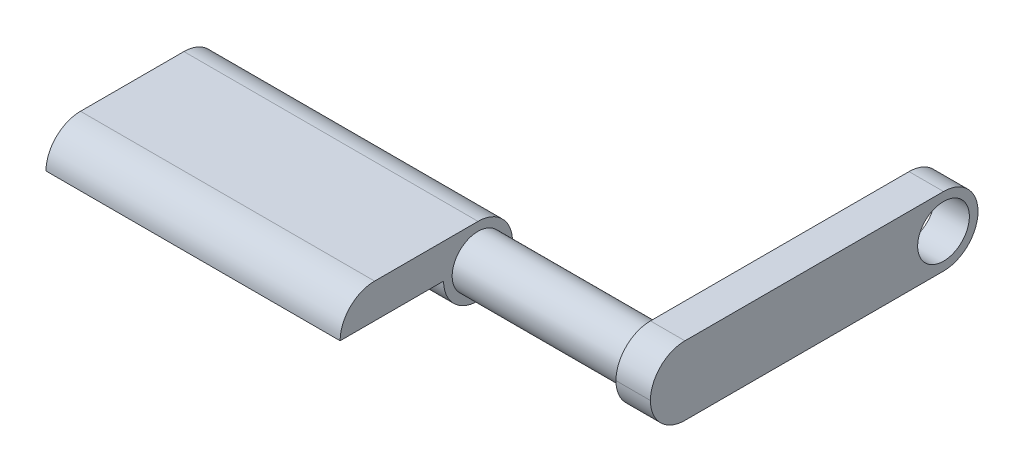
SolidWorks part; units mm, degrees
material "Nickel"
ref_plane "Front Plane" through (0, 0, 0) normal (0, 0, 1) x (1, 0, 0)
ref_plane "Top Plane" through (0, 0, 0) normal (0, 1, 0) x (1, 0, 0)
ref_plane "Right Plane" through (0, 0, 0) normal (1, 0, 0) x (0, 0, -1)
sketch "Sketch2" plane through (0, 0, 0) normal (1, 0, 0) x (0, 0, -1)
  circle A0 centre (0, 0) radius 2
  dimension "D1" = 4
extrude "Boss-Extrude1" add sketch "Sketch2" along normal blind 17.06
sketch "Sketch3" plane through (17.06, 0, 0) normal (1, 0, 0) x (0, 0, -1)
  circle A0 centre (0, 0) radius 1.5
  dimension "D1" = 3
extrude "Boss-Extrude2" add sketch "Sketch3" along normal blind 12
sketch "Sketch4" plane through (29.06, 0, 0) normal (1, 0, 0) x (0, 0, -1)
  line L1 (-2, 2) -> (1.9881, 2)
  line L2 (-2, 2) -> (-2, -2)
  line L3 (-2, -2) -> (1.9881, -2)
  line L4 (1.9881, 2) -> (1.9881, -2)
  circle A0 centre (0, 0) radius 2 construction
extrude "Boss-Extrude3" add sketch "Sketch4" against normal blind 2
sketch "Sketch5" plane through (0, 0, 2) normal (0, 0, 1) x (1, 0, 0)
  line L1 (29.06, 2) -> (27.06, 2)
  line L2 (29.06, 2) -> (29.06, -2)
  line L3 (29.06, -2) -> (27.06, -2)
  line L4 (27.06, 2) -> (27.06, -2)
extrude "Boss-Extrude4" add sketch "Sketch5" against normal blind 19
fillet "Fillet1" radius 2 1 edges at (28.06, 2, 2)
fillet "Fillet2" radius 2 1 edges at (28.06, -2, 2)
fillet "Fillet3" radius 2 2 edges at (28.06, -2, -17) (28.06, 2, -17)
sketch "Sketch6" plane through (29.06, 0, 0) normal (1, 0, 0) x (0, 0, -1)
  circle A0 centre (15, 0) radius 1.5
  arc A1 (17, 0) -> (15, 2) centre (15, 0) ccw construction
  dimension "D1" = 3
extrude "Cut-Extrude1" cut sketch "Sketch6" against normal through all
sketch "Sketch7" plane through (29.06, 0, 0) normal (1, 0, 0) x (0, 0, -1)
  line L0 (17, 0) -> (22, -8.6603)
  line L1 (13.5359, -2) -> (18.5359, -10.6603)
  line L2 (0, -2) -> (15, -2) construction
  line L3 (13.5359, -2) -> (15, -2)
  line L4 (18.5359, -10.6603) -> (22, -8.6603)
  line L6 (0, -2) -> (15, -2)
  line L7 (15, 2) -> (0, 2)
  line L8 (0, -2) -> (13.5359, -2)
  line L9 (15, 2) -> (0, 2)
  circle A0 centre (15, 0) radius 2
  arc A4 (15, -2) -> (17, 0) centre (15, 0) ccw
  arc A5 (17, 0) -> (15, 2) centre (15, 0) ccw
  arc A6 (0, 2) -> (-2, 0) centre (0, 0) ccw
  arc A7 (-2, 0) -> (0, -2) centre (0, 0) ccw
  arc A9 (17, 0) -> (15, 2) centre (15, 0) ccw
  arc A10 (0, 2) -> (-2, 0) centre (0, 0) ccw
  arc A11 (-2, 0) -> (0, -2) centre (0, 0) ccw
  line M11 (0, -2) -> (15, -2)
  arc M12 (15, -2) -> (17, 0) centre (15, 0) ccw
  dimension "D4" = 120
  dimension "D1" = 4
  dimension "D2" = 10
  dimension "D3" = 0
extrude "Boss-Extrude5" [suppressed] add sketch "Sketch7" against normal blind 2 contours L1 L4 L0 M12 M11
fillet "Fillet4" [suppressed] radius 2
fillet "Fillet5" [suppressed] radius 2
sketch "Sketch8" [suppressed] plane through (20, 0, 0) normal (1, 0, 0) x (0, 0, -1)
  circle A0 centre (15.2679, -7.9282) radius 1.5
  arc A1 (16.2679, -9.6603) -> (17, -6.9282) centre (15.2679, -7.9282) ccw construction
  dimension "D1" = 3
extrude "Boss-Extrude6" [suppressed] add sketch "Sketch8" along normal blind 36
sketch "Sketch9" [suppressed] plane through (56, 0, 0) normal (1, 0, 0) x (0, 0, -1)
  line L0 (17, -6.9282) -> (13, 0)
  line L1 (9.5359, -2) -> (13.5359, -8.9282)
  line L2 (9.5359, -2) -> (9, 0)
  circle A0 centre (15.2679, -7.9282) radius 2
  circle A1 centre (11, 0) radius 2
  circle A2 centre (11, 0) radius 1.5
  circle M1 centre (15.2679, -7.9282) radius 1.5
  dimension "D1" = 3
extrude "Boss-Extrude7" [suppressed] add sketch "Sketch9" along normal blind 1.5 and the other way blind 1.5 contours A0 M1 | A1 L2 L1 A0 L0 | A1 L2 A2 | M1
sketch "Sketch10" plane through (0, 0, 0) normal (-1, 0, 0) x (0, 0, 1)
  line L1 (0, 2) -> (8, 2)
  line L2 (0, 2) -> (0, 0)
  line L3 (0, 0) -> (8, 0)
  line L4 (8, 2) -> (8, 0)
  dimension "D1" = 8
extrude "Boss-Extrude8" add sketch "Sketch10" against normal up to surface (17.06 mm away) up to face at (17.06, 0, -1.5)
fillet "Fillet6" radius 2 1 edges at (8.53, 2, 8)
